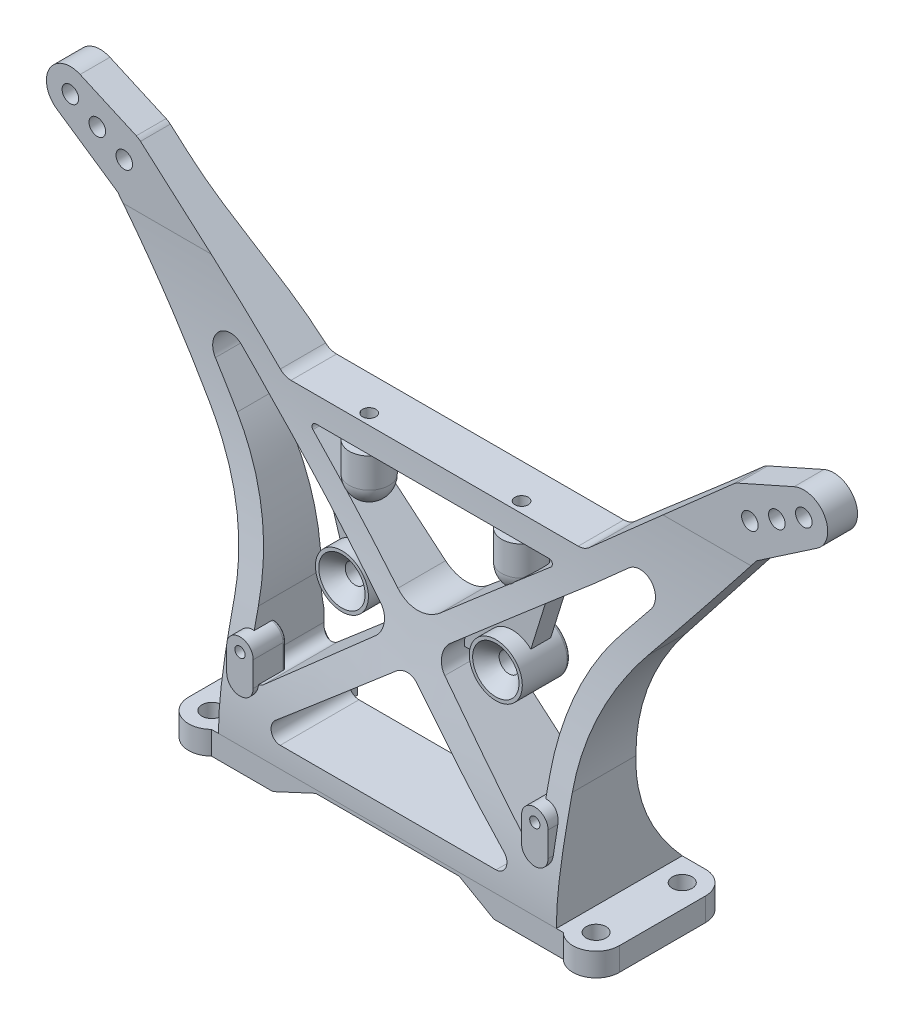
SolidWorks part; units mm, degrees
ref_plane "Front Plane" through (0, 0, 0) normal (0, 0, 1) x (1, 0, 0)
ref_plane "Top Plane" through (0, 0, 0) normal (0, 1, 0) x (1, 0, 0)
ref_plane "Right Plane" through (0, 0, 0) normal (1, 0, 0) x (0, 0, -1)
sketch "Sketch3" plane through (0, 0, 0) normal (0, 0, 1) x (1, 0, 0)
  line L0 (-16.289, -29.1062) -> (16.289, -29.1062)
  line L1 (17.2472, -26.4522) -> (1.597, -13.4575)
  line L2 (-1.597, -13.4575) -> (-17.2472, -26.4522)
  line L3 (32.5, -35.6062) -> (-32.5, -35.6062)
  line L4 (0, -35.6062) -> (0, 0) construction
  line L5 (-17.276, -35.6062) -> (-10.8295, -32.6062)
  line L6 (-10.8295, -32.6062) -> (10.8295, -32.6062)
  line L7 (10.8295, -32.6062) -> (16.0567, -35.6062)
  line L8 (0, -32.6062) -> (0, 0) construction
  line L9 (32.5, -35.6062) -> (32.5, -32.1062)
  line L10 (32.5, -32.1062) -> (25.5, -32.1062)
  line L11 (-32.5, -35.6062) -> (-32.5, -32.1062)
  line L12 (-32.5, -32.1062) -> (-25.5, -32.1062)
  line L13 (-25.5, -32.1062) -> (-25.5, -15.5226)
  line L14 (25.5, -32.1062) -> (-25.5, -32.1062) construction
  line L15 (0, -32.1062) -> (0, 0) construction
  line L16 (25.5, -32.1062) -> (25.5, -15.5226)
  line L17 (48.2113, 23.5519) -> (33.0635, 4.2389)
  line L18 (48.2113, 23.5519) -> (57.3809, 29.792)
  line L19 (53.8787, 36.0818) -> (45.3992, 32.3095)
  line L20 (47.2129, 28.2727) -> (55.3477, 32.7798) construction
  line L21 (44.7626, 31.9011) -> (23.3308, 13.018)
  line L22 (21.6781, 12.3938) -> (-21.6781, 12.3938)
  line L23 (-17.6357, 8.8938) -> (17.6357, 8.8938)
  line L24 (24.247, 8.8938) -> (29.2451, 13.2975)
  line L25 (32.8714, 9.8727) -> (29.0184, 4.9603)
  line L26 (22, -14.978) -> (22, -22.0285)
  line L27 (55.3477, 36.3938) -> (64.3873, 36.3938) construction
  line L28 (0, -29.1062) -> (0, 0) construction
  line L29 (24.247, 8.8938) -> (5.2406, -7.0999)
  line L30 (5.2234, -10.9109) -> (19.5239, -23.1674)
  line L31 (0, 8.8938) -> (0, 0) construction
  line L32 (0, 12.3938) -> (0, 0) construction
  line L33 (-55.3477, 36.3938) -> (-64.3873, 36.3938) construction
  line L34 (-47.2129, 28.2727) -> (-55.3477, 32.7798) construction
  line L35 (-5.2234, -10.9109) -> (-19.5239, -23.1674)
  line L36 (-24.247, 8.8938) -> (-5.2406, -7.0999)
  line L37 (-22, -14.978) -> (-22, -22.0285)
  line L38 (-32.8714, 9.8727) -> (-29.0184, 4.9603)
  line L39 (-24.247, 8.8938) -> (-29.2451, 13.2975)
  line L40 (-44.7626, 31.9011) -> (-23.3308, 13.018)
  line L41 (-53.8787, 36.0818) -> (-45.3992, 32.3095)
  line L42 (-48.2113, 23.5519) -> (-57.3809, 29.792)
  line L43 (-48.2113, 23.5519) -> (-33.0635, 4.2389)
  line L44 (-17.9576, 8.0112) -> (-3.2193, -4.3909)
  line L45 (3.2193, -4.3909) -> (17.9576, 8.0112)
  line L46 (0, 8.8938) -> (0, 0) construction
  arc A0 (57.3809, 29.792) -> (53.8787, 36.0818) centre (55.3477, 32.7798) ccw
  circle A1 centre (55.3477, 32.7798) radius 1.25
  circle A2 centre (51.2803, 30.5262) radius 1.25
  circle A3 centre (47.2129, 28.2727) radius 1.25
  arc A4 (29.2451, 13.2975) -> (32.8714, 9.8727) centre (30.9008, 11.4184) cw
  arc A5 (5.2406, -7.0999) -> (5.2234, -10.9109) centre (6.8503, -9.0127) ccw
  arc A6 (1.597, -13.4575) -> (-1.597, -13.4575) centre (0, -15.3809) ccw
  arc A7 (-17.2472, -26.4522) -> (-16.289, -29.1062) centre (-16.289, -27.6062) ccw
  arc A8 (22, -22.0285) -> (19.5239, -23.1674) centre (20.5, -22.0285) cw
  arc A9 (16.289, -29.1062) -> (17.2472, -26.4522) centre (16.289, -27.6062) ccw
  arc A10 (-5.2406, -7.0999) -> (-5.2234, -10.9109) centre (-6.8503, -9.0127) cw
  arc A11 (-22, -22.0285) -> (-19.5239, -23.1674) centre (-20.5, -22.0285) ccw
  arc A12 (-29.2451, 13.2975) -> (-32.8714, 9.8727) centre (-30.9008, 11.4184) ccw
  circle A13 centre (-47.2129, 28.2727) radius 1.25
  circle A14 centre (-51.2803, 30.5262) radius 1.25
  circle A15 centre (-55.3477, 32.7798) radius 1.25
  arc A16 (-57.3809, 29.792) -> (-53.8787, 36.0818) centre (-55.3477, 32.7798) cw
  arc A17 (-3.2193, -4.3909) -> (3.2193, -4.3909) centre (0, -0.5652) ccw
  arc A18 (17.6357, 8.8938) -> (17.9576, 8.0112) centre (17.6357, 8.3938) cw
  arc A19 (-17.9576, 8.0112) -> (-17.6357, 8.8938) centre (-17.6357, 8.3938) cw
  arc A20 (45.3992, 32.3095) -> (44.7626, 31.9011) centre (46.4154, 30.0253) ccw
  arc A21 (-44.7626, 31.9011) -> (-45.3992, 32.3095) centre (-46.4154, 30.0253) ccw
  arc A22 (23.3308, 13.018) -> (21.6781, 12.3938) centre (21.6781, 14.8938) cw
  arc A23 (-21.6781, 12.3938) -> (-23.3308, 13.018) centre (-21.6781, 14.8938) cw
  spline S0 degree 3 poles (25.5, -15.5226) (25.5, -7.9528) (28.6451, -1.3945) (33.0635, 4.2389) knots 0 0 0 0 1 1 1 1
  spline S1 degree 3 poles (22, -14.978) (22, -7.3515) (24.5868, -0.6899) (29.0184, 4.9603) knots 0 0 0 0 1 1 1 1
  spline S2 degree 3 poles (-22, -14.978) (-22, -7.3515) (-24.5868, -0.6899) (-29.0184, 4.9603) knots 0 0 0 0 1 1 1 1
  spline S3 degree 3 poles (-25.5, -15.5226) (-25.5, -7.9528) (-28.6451, -1.3945) (-33.0635, 4.2389) knots 0 0 0 0 1 1 1 1
  point P90 (0, -7.0999)
  point P97 (45.0497, 32.154)
  point P100 (-45.0497, 32.154)
  point P103 (22.6223, 12.3938)
  point P106 (-22.6223, 12.3938)
  dimension "D7" = 2.5
  dimension "D8" = 2.5
  dimension "D9" = 2.5
  dimension "D15" = 2.5
  dimension "D16" = 1.5
  dimension "D18" = 5
  dimension "D19" = 0.5
  dimension "D20" = 2.5
  dimension "D2" = 65
  dimension "D3" = 3
  dimension "D4" = 3.5
  dimension "D5" = 3.5
  dimension "D6" = 32.6062
  dimension "D10" = 72
  dimension "D11" = 48
  dimension "D12" = 3.5
  dimension "D13" = 25.5
  dimension "D14" = 3.5
  dimension "D17" = 45.2446
extrude "Boss-Extrude2" add sketch "Sketch3" along normal blind 8.5 and the other way blind 11.5 contours S3 L13 L12 L11 L3 L5 L6 L7 L9 L10 L16 S0 L17 L18 A0 L19 A20 L21 A22 L22 A23 L40 A21 L41 A16 L42 L43 S1 L26 A8 L30 A5 L29 L24 A4 L25 A14 A1 A2 A3 A9 L0 A7 L2 region at (24.2784, -34.2246, 0)
sketch "Sketch4" plane through (0, 0, 0) normal (1, 0, 0) x (0, 0, -1)
  line L0 (-8.5, -32.1062) -> (-7.5, -32.1062)
  line L1 (0, 36.3938) -> (0, 22.4957)
  line L2 (11.5, 36.3938) -> (-8.5, 36.3938) construction
  line L3 (0, 36.3938) -> (-8.5, 36.3938)
  line L4 (-8.5, 36.3938) -> (-8.5, 29.792) construction
  line L5 (-8.5, 36.3938) -> (-8.5, -32.1062)
  line L6 (4.5, 36.3938) -> (4.5, -16.1942)
  line L7 (4.5, 36.3938) -> (11.5, 36.3938)
  line L8 (11.5, 29.792) -> (11.5, 36.3938) construction
  line L9 (11.5, 36.3938) -> (11.5, -32.1062)
  line L10 (11.5, -32.1062) -> (-8.5, -32.1062) construction
  line L11 (-7.5, -32.1062) -> (-7.5, -34.5604) construction
  spline S0 degree 3 poles (-7.5, -32.1062) (-7.5, -18.2378) (0, -3.8629) (0, 22.4957) knots 0 0 0 0 1 1 1 1
  spline S1 degree 2 poles (4.5, -16.1942) (4.5, -24.3843) (11.5, -32.1062) knots 0 0 0 1 1 1
  dimension "D1" = 4.5
  dimension "D2" = 1
extrude "Cut-Extrude1" cut sketch "Sketch4" against normal through all and the other way through all contours L5 L1 L3 | L6 S1 region at (0, 10.6256, 4.9394) region at (0, 4.6469, -8.1165)
sketch "Sketch5" plane through (0, -35.6062, 0) normal (0, -1, 0) x (1, 0, 0)
  line L0 (-30.5, 5) -> (-30.5, 1.3765) construction
  line L1 (-29, 6.5) -> (-22.1667, 6.5) construction
  line L2 (-17.276, 8.5) -> (-32.5, 8.5) construction
  line L3 (-32.5, -11.5) -> (-32.5, 8.5) construction
  line L4 (-29, 3.5) -> (-29, -6.5) construction
  line L5 (-27.5, -8) -> (27.5, -8) construction
  line L6 (29, -6.5) -> (29, 3.5) construction
  line L7 (27.5, 5) -> (-27.5, 5) construction
  line L8 (-29, -9.5) -> (-25.3589, -9.5) construction
  line L9 (-17.276, -11.5) -> (-32.5, -11.5) construction
  line L10 (30.5, 5) -> (30.5, 0.9382) construction
  line L11 (32.5, -11.5) -> (32.5, 8.5) construction
  line L12 (32.5, -11.5) -> (16.0567, -11.5) construction
  line L13 (32.5, 8.5) -> (16.0567, 8.5) construction
  line L14 (26.5505, 7.5) -> (-26.5505, 7.5)
  line L15 (-29, -11.5) -> (-23.5, -11.5)
  line L16 (-23.5, -11.5) -> (-23.5, -7.5)
  line L17 (-20.5, -4.5) -> (-9.3284, -4.5)
  line L18 (-7.9142, -3.9142) -> (-6.0858, -2.0858)
  line L19 (-4.6716, -1.5) -> (4.6716, -1.5)
  line L20 (-33.0635, -4.5) -> (-48.2113, -4.5) construction
  line L21 (0, -1.5) -> (0, 0) construction
  line L22 (23.5, -11.5) -> (23.5, -7.5)
  line L23 (20.5, -4.5) -> (9.3284, -4.5)
  line L24 (7.9142, -3.9142) -> (6.0858, -2.0858)
  line L25 (-23.5, -11.5) -> (23.5, -11.5)
  line L26 (-29, -11.5) -> (-32.5, -11.5)
  line L27 (-32.5, -11.5) -> (-32.5, -8)
  line L28 (-32.5, 5) -> (-32.5, 8.5)
  line L29 (-32.5, 8.5) -> (-29, 8.5)
  line L30 (-29, 8.5) -> (29, 8.5)
  line L31 (29, 8.5) -> (32.5, 8.5)
  line L32 (32.5, 8.5) -> (32.5, 5)
  line L33 (32.5, -8) -> (32.5, -11.5)
  line L34 (32.5, -11.5) -> (29, -11.5)
  line L35 (9.3284, -4.5) -> (-9.3284, -4.5)
  circle A0 centre (-29, -8) radius 1.5
  circle A1 centre (-29, 5) radius 1.5
  circle A2 centre (29, 5) radius 1.5
  circle A3 centre (29, -8) radius 1.5
  arc A4 (-32.5, 5) -> (-29, 8.5) centre (-29, 5) cw
  arc A5 (-32.5, -8) -> (-29, -11.5) centre (-29, -8) ccw
  arc A6 (32.5, -8) -> (29, -11.5) centre (29, -8) cw
  arc A7 (32.5, 5) -> (29, 8.5) centre (29, 5) ccw
  arc A8 (-29, 8.5) -> (-26.5505, 7.5) centre (-29, 5) cw
  arc A9 (29, 8.5) -> (26.5505, 7.5) centre (29, 5) ccw
  arc A10 (-20.5, -4.5) -> (-23.5, -7.5) centre (-20.5, -7.5) ccw
  arc A11 (-4.6716, -1.5) -> (-6.0858, -2.0858) centre (-4.6716, -3.5) ccw
  arc A12 (-7.9142, -3.9142) -> (-9.3284, -4.5) centre (-9.3284, -2.5) cw
  arc A13 (20.5, -4.5) -> (23.5, -7.5) centre (20.5, -7.5) cw
  arc A14 (7.9142, -3.9142) -> (9.3284, -4.5) centre (9.3284, -2.5) ccw
  arc A15 (4.6716, -1.5) -> (6.0858, -2.0858) centre (4.6716, -3.5) cw
  point P55 (-23.5, -4.5)
  point P60 (-5.5, -1.5)
  point P63 (-8.5, -4.5)
  point P71 (8.5, -4.5)
  line M17 (32.5, -11.5) -> (32.5, 8.5)
  line M18 (32.5, 8.5) -> (16.0567, 8.5)
  line M19 (16.0567, 8.5) -> (16.0567, -11.5)
  line M20 (16.0567, -11.5) -> (32.5, -11.5)
  dimension "D3" = 3
  dimension "D4" = 3
  dimension "D5" = 3
  dimension "D6" = 3
  dimension "D14" = 3
  dimension "D15" = 2
  dimension "D1" = 2
  dimension "D2" = 2
  dimension "D7" = 2
  dimension "D8" = 2
  dimension "D9" = 1
  dimension "D10" = 9
  dimension "D11" = 15
  dimension "D12" = 3
  dimension "D13" = 5.5
extrude "Cut-Extrude2" cut sketch "Sketch5" against normal through all contours A13 L23 L22 M19 M20 | L17 A10 L16 L25 L23 L35 M19 | A3 | A6 M17 M20 | A7 M17 M18 | A2 | A9 L14 M18 M19 | L30 A8 L14 M19 | L28 A4 L29 | A1 | A0 | A5 L27 L26 region at (21.6996, -35.6062, 8.0142) region at (-31.7182, -35.6062, 7.7182) region at (-31.7182, -35.6062, -10.7182) region at (-5.6323, -35.6062, 8.0037) region at (31.7182, -35.6062, 7.7182) region at (-3.5874, -35.6062, -8.0199) region at (19.6609, -35.6062, -8.1089) region at (31.7182, -35.6062, -10.7182) region at (-29, -35.6062, -8) region at (-29, -35.6062, 5) region at (29, -35.6062, 5) region at (29, -35.6062, -8)
ref_plane "Plane2" through (0, 0, -2.25) normal (0, 0, -1) x (-1, 0, 0)
sketch "Sketch7" plane through (0, 0, -4.5) normal (0, 0, -1) x (-1, 0, 0)
  line L8 (-21.6781, 12.3938) -> (21.6781, 12.3938)
  line L9 (-44.7626, 31.9011) -> (-23.3308, 13.018)
  line L10 (-21.6781, 12.3938) -> (21.6781, 12.3938)
  line L11 (-44.7626, 31.9011) -> (-23.3308, 13.018)
  line L12 (23.3308, 13.018) -> (44.7626, 31.9011)
  line L13 (23.3308, 13.018) -> (44.7626, 31.9011)
  line L14 (17.6357, 8.8938) -> (22.3586, 8.8938)
  line L15 (-17.6357, 8.8938) -> (17.6357, 8.8938)
  line L16 (-17.6357, 8.8938) -> (17.6357, 8.8938)
  line L17 (-17.6357, 8.8938) -> (-22.3586, 8.8938)
  line L20 (-29.2451, 13.2975) -> (-24.247, 8.8938)
  line L21 (-29.2451, 13.2975) -> (-25.664, 10.1422)
  line L22 (29.2451, 13.2975) -> (44.5347, 26.7688)
  line L23 (29.2451, 13.2975) -> (24.247, 8.8938)
  line L24 (29.2451, 13.2975) -> (25.664, 10.1422)
  line L25 (44.5347, 26.7688) -> (42.0886, 29.5451)
  line L26 (-29.2451, 13.2975) -> (-44.5347, 26.7688)
  line L27 (-44.5347, 26.7688) -> (-42.0886, 29.5451)
  arc A4 (22.3586, 8.8938) -> (25.664, 10.1422) centre (22.3586, 13.8938) ccw
  arc A5 (-25.664, 10.1422) -> (-22.3586, 8.8938) centre (-22.3586, 13.8938) ccw
  arc A6 (21.6781, 12.3938) -> (23.3308, 13.018) centre (21.6781, 14.8938) ccw
  arc A7 (-23.3308, 13.018) -> (-21.6781, 12.3938) centre (-21.6781, 14.8938) ccw
  arc A8 (21.6781, 12.3938) -> (23.3308, 13.018) centre (21.6781, 14.8938) ccw
  arc A9 (-23.3308, 13.018) -> (-21.6781, 12.3938) centre (-21.6781, 14.8938) ccw
  dimension "D8" = 5
  dimension "D6" = 25
  dimension "D7" = 25
  dimension "D1" = 0
  dimension "D2" = 0
  dimension "D3" = 0
  dimension "D4" = 0
  dimension "D5" = 0
extrude "Boss-Extrude3" add sketch "Sketch7" along normal blind 2 contours A9 L11 L27 L26 L21 A5 L17 L16 L14 A4 L24 L22 L25 L13 A8 L10 region at (0, 11.4794, -4.5)
sketch "Sketch8" plane through (3.7391, -4.2438, 0) normal (-0.6611, 0.7503, 0) x (0.7503, 0.6611, 0)
  line L0 (26.1113, 6.5) -> (22.2063, 6.5) construction
  line L1 (24.4586, 6.5) -> (-8.072, 6.5) construction
  line L2 (51.1113, 4.5) -> (53.234, 4.5) construction
  line L3 (51.1113, 4.5) -> (54.6753, 4.5) construction
  line L4 (26.1113, 6.5) -> (51.1113, 6.5)
  line L5 (51.1113, 6.5) -> (51.1113, 4.5)
  spline S0 degree 3 poles (26.1113, 6.5) (34.5244, 6.5) (42.7514, 4.5) (51.1113, 4.5) knots 0 0 0 0 1 1 1 1
extrude "Cut-Extrude3" cut sketch "Sketch8" against normal up to surface (3.7002 mm away) up to face at (30.6103, 14.5003, -3.7264)
mirror "Mirror1" about plane through (0, 0, 0) normal (1, 0, 0) of "Cut-Extrude3"
ref_plane "Plane3" through (0, 0, -1.25) normal (0, 0, 1) x (1, 0, 0)
sketch "Sketch10" plane through (0, 0, -1.25) normal (0, 0, 1) x (1, 0, 0)
  line L0 (-11.5, 8.8938) -> (-11.5, 1.4265)
  line L2 (-8.5, 4.4265) -> (-8.5, 8.8938)
  line L3 (-8.5, 8.8938) -> (-11.5, 8.8938)
  arc A0 (-11.5, 1.4265) -> (-8.5, 4.4265) centre (-11.5, 4.4265) ccw
  dimension "D2" = 3
  dimension "D1" = 11.5
revolve "Revolve1" add sketch "Sketch10" angle 360 about L0 region at (-10.0783, 5.4492, -1.25)
mirror "Mirror3" about plane through (0, 0, 0) normal (1, 0, 0) of "Revolve1"
sketch "Sketch11" plane through (0, 12.3938, 0) normal (0, 1, 0) x (1, 0, 0)
  line L0 (11.5, 1.25) -> (-11.5, 1.25) construction
  line L1 (0, 0) -> (0, 1.25) construction
  circle A0 centre (-11.5, 1.25) radius 1
  circle A1 centre (11.5, 1.25) radius 1
  dimension "D2" = 2
  dimension "D3" = 2
  dimension "D1" = 1.25
  dimension "D4" = 23
extrude "Cut-Extrude4" cut sketch "Sketch11" against normal blind 8
sketch "Sketch13" plane through (0, 0, -1.25) normal (0, 0, 1) x (1, 0, 0)
  line L0 (-16.661, 2.5102) -> (-12.967, -9.4)
  line L1 (-24.247, 8.8938) -> (-5.2406, -7.0999) construction
  line L2 (-12.967, -9.4) -> (12.967, -9.4)
  line L3 (12.967, -9.4) -> (16.661, 2.5102)
  line L4 (5.2406, -7.0999) -> (24.247, 8.8938) construction
  line L5 (-16.661, 2.5102) -> (16.661, 2.5102) construction
  line L8 (-5.2406, -7.0999) -> (-24.247, 8.8938)
  line L9 (-5.2406, -7.0999) -> (-24.247, 8.8938)
  line L11 (0, -9.4) -> (0, 0) construction
  line L12 (24.247, 8.8938) -> (5.2406, -7.0999)
  line L13 (24.247, 8.8938) -> (5.2406, -7.0999)
  arc A2 (-5.2234, -10.9109) -> (-5.2406, -7.0999) centre (-6.8503, -9.0127) ccw
  arc A3 (-5.2234, -10.9109) -> (-5.2406, -7.0999) centre (-6.8503, -9.0127) ccw
  arc A4 (5.2406, -7.0999) -> (5.2234, -10.9109) centre (6.8503, -9.0127) ccw
  arc A5 (5.2406, -7.0999) -> (5.2234, -10.9109) centre (6.8503, -9.0127) ccw
  dimension "D2" = 9.4
  dimension "D1" = 0
  dimension "D3" = 0
extrude "Boss-Extrude5" add sketch "Sketch13" along normal blind 1.5 and the other way blind 1.5 contours L13 A5 L2 L3 | L2 A3 L9 L0 region at (-10.8954, -5.3406, -1.25) region at (10.8954, -5.3406, -1.25)
sketch "Sketch14" plane through (0, 0, 0.25) normal (0, 0, 1) x (1, 0, 0)
  line L0 (11.614, -7.6515) -> (-11.614, -7.6515) construction
  line L1 (0, -7.6515) -> (0, 0) construction
  circle A0 centre (-11.614, -7.6515) radius 4
  circle A1 centre (11.614, -7.6515) radius 4
  dimension "D1" = 8
  dimension "D2" = 8
extrude "Boss-Extrude6" add sketch "Sketch14" along normal blind 2.5 and the other way up to surface (4.75 mm away) other way up to face at (0, -23.0213, -4.5)
sketch "Sketch15" plane through (0, 0, 2.75) normal (0, 0, 1) x (1, 0, 0)
  circle A0 centre (-11.614, -7.6515) radius 1.5
  circle A1 centre (11.614, -7.6515) radius 1.5
  circle A2 centre (11.614, -7.6515) radius 4 construction
  circle A3 centre (-11.614, -7.6515) radius 4 construction
  dimension "D1" = 3
  dimension "D2" = 3
extrude "Cut-Extrude5" cut sketch "Sketch15" against normal through all
chamfer "Chamfer1" distance 2 angle 45 2 edges at (13.114, -7.6515, 2.75) (-10.114, -7.6515, 2.75)
fillet "Fillet1" radius 0.5 2 edges at (-11.614, -11.6515, -4.5) (11.614, -11.6515, -4.5)
sketch "Sketch16" plane through (0, 0, 7.5) normal (0, 0, 1) x (1, 0, 0)
  line L0 (-22.25, -19.8562) -> (-22.25, -23.6062) construction
  line L1 (-20.25, -19.8562) -> (-20.25, -23.6062)
  line L2 (-24.25, -19.8562) -> (-24.25, -23.6062)
  line L3 (-17.276, -35.6062) -> (-26.5505, -35.6062) construction
  line L4 (-25.5, -15.5226) -> (-25.5, -32.1062) construction
  arc A0 (-20.25, -19.8562) -> (-24.25, -19.8562) centre (-22.25, -19.8562) ccw
  arc A1 (-24.25, -23.6062) -> (-20.25, -23.6062) centre (-22.25, -23.6062) ccw
  point P2 (-22.25, -21.7312)
  point P9 (-24.25, -21.7312)
  dimension "D1" = 12
  dimension "D2" = 4
  dimension "D3" = 1.25
  dimension "D4" = 15.75
extrude "Boss-Extrude7" add sketch "Sketch16" against normal blind 5 contours A0 L2 A1 L1
fillet "Fillet2" radius 0.5 2 edges at (-20.25, -21.6819, 2.5) (-20.75, -18.5334, 2.5)
sketch "Sketch17" plane through (0, 0, 7.5) normal (0, 0, 1) x (1, 0, 0)
  circle A0 centre (-22.25, -19.8562) radius 0.7707
  arc A1 (-20.25, -19.8562) -> (-24.25, -19.8562) centre (-22.25, -19.8562) ccw construction
extrude "Cut-Extrude6" cut sketch "Sketch17" against normal blind 4 contours A0
mirror "Mirror5" about plane through (0, 0, 0) normal (1, 0, 0) of "Cut-Extrude6", "Fillet2", "Boss-Extrude7"
ref_axis "Axis1" through (-11.5, 4.3938, -1.25) along (0, 1, 0)
ref_axis "Axis2" through (11.5, 4.3938, -1.25) along (0, 1, 0)
ref_plane "Plane4" through (0, 0, -1.25) normal (0, 0, -1) x (-1, 0, 0)
